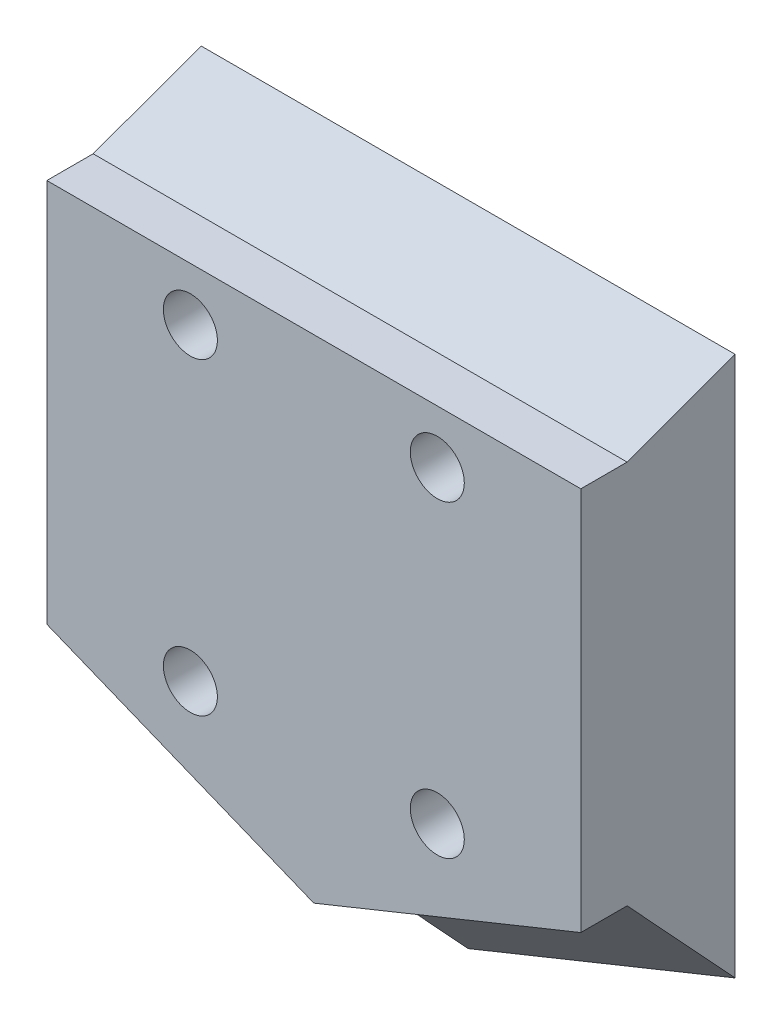
SolidWorks part; units mm, degrees
ref_plane "Plano frontal" through (0, 0, 0) normal (0, 0, 1) x (1, 0, 0)
ref_plane "Plano superior" through (0, 0, 0) normal (0, 1, 0) x (1, 0, 0)
ref_plane "Plano direito" through (0, 0, 0) normal (1, 0, 0) x (0, 0, -1)
sketch "Esboço1" plane through (0, 0, 0) normal (0, 0, 1) x (1, 0, 0)
  line L1 (-17.3, 13) -> (17.3, 13)
  line L2 (-17.3, 13) -> (-17.3, -13)
  line L3 (-17.3, -13) -> (17.3, -13)
  line L4 (17.3, 13) -> (17.3, -13)
  line L5 (-17.3, 13) -> (17.3, -13) construction
  line L6 (-17.3, -13) -> (17.3, 13) construction
  point P0 (0, 0)
  dimension "D1" = 34.6
  dimension "D2" = 26
extrude "Ressalto-extrusão1" add sketch "Esboço1" along normal blind 7
sketch "Esboço10" plane through (0, 0, 0) normal (0, 0, -1) x (-1, 0, 0)
  line L0 (-17.3, -19.5) -> (0, -26.5)
  line L1 (-17.3, 13) -> (17.3, 13)
  line L2 (-17.3, 13) -> (-17.3, 15.5)
  line L3 (-17.3, 15.5) -> (17.3, 15.5)
  line L4 (17.3, 13) -> (17.3, 15.5)
  line L5 (0, -26.5) -> (17.3, -19.5)
  line L6 (-17.3, -19.5) -> (-17.3, -13)
  line L7 (-17.3, -13) -> (17.3, -13)
  line L8 (17.3, -13) -> (17.3, -19.5)
  dimension "D1" = 7
  dimension "D2" = 35
  dimension "D3" = 2.5
extrude "Ressalto-extrusão4" add sketch "Esboço10" against normal up to surface (7 mm away) up to face at (0, 0, 7)
chamfer "Chanfro1" distance 7 angle 45 2 edges at (8.65, -23, 7) (-8.65, -23, 7)
chamfer "Chanfro2" distance 7 angle 20 1 edges at (0, 15.5, 7) first distance on face at (0, 15.5, 3.5)
sketch "Esboço13" plane through (0, 0, 7) normal (0, 0, 1) x (1, 0, 0)
  line L5 (17.3, -11.9487) -> (17.3, 12.9522)
  line L6 (17.3, 12.9522) -> (-17.3, 12.9522)
  line L7 (-17.3, 12.9522) -> (-17.3, -11.9487)
  line L8 (-17.3, -11.9487) -> (0, -18.9487)
  line L9 (0, -18.9487) -> (17.3, -11.9487)
  line L10 (17.3, -11.9487) -> (17.3, 12.9522)
  line L11 (17.3, 12.9522) -> (-17.3, 12.9522)
  line L12 (-17.3, 12.9522) -> (-17.3, -11.9487)
  line L13 (-17.3, -11.9487) -> (0, -18.9487)
  line L14 (0, -18.9487) -> (17.3, -11.9487)
  dimension "D1" = 0
extrude "Ressalto-extrusão5" add sketch "Esboço13" along normal blind 3
sketch "Esboço11" plane through (0, 0, 10) normal (0, 0, 1) x (1, 0, 0)
  line L0 (0, 9.9803) -> (0, 0) construction
  line L2 (-17.3, 15.5) -> (17.3, 15.5) construction
  circle A0 centre (8, 9.5) radius 1.75
  circle A1 centre (8, -10.5) radius 1.75
  circle A2 centre (-8, -10.5) radius 1.75
  circle A3 centre (-8, 9.5) radius 1.75
  point P11 (12.5, 10.6425)
  point P12 (12.5, 9.0973)
  dimension "D1" = 3.5
  dimension "D2" = 20
  dimension "D3" = 16
  dimension "D4" = 6
extrude "Corte-extrusão1" cut sketch "Esboço11" against normal blind 10
sketch "Esboço12" plane through (0, 0, 0) normal (0, 0, -1) x (-1, 0, 0)
  circle A0 centre (-8, 9.5) radius 3.5
  circle A1 centre (8, 9.5) radius 3.5
  circle A2 centre (-8, -10.5) radius 3.5
  circle A3 centre (8, -10.5) radius 3.5
  dimension "D1" = 7
extrude "Corte-extrusão2" cut sketch "Esboço12" against normal blind 3
